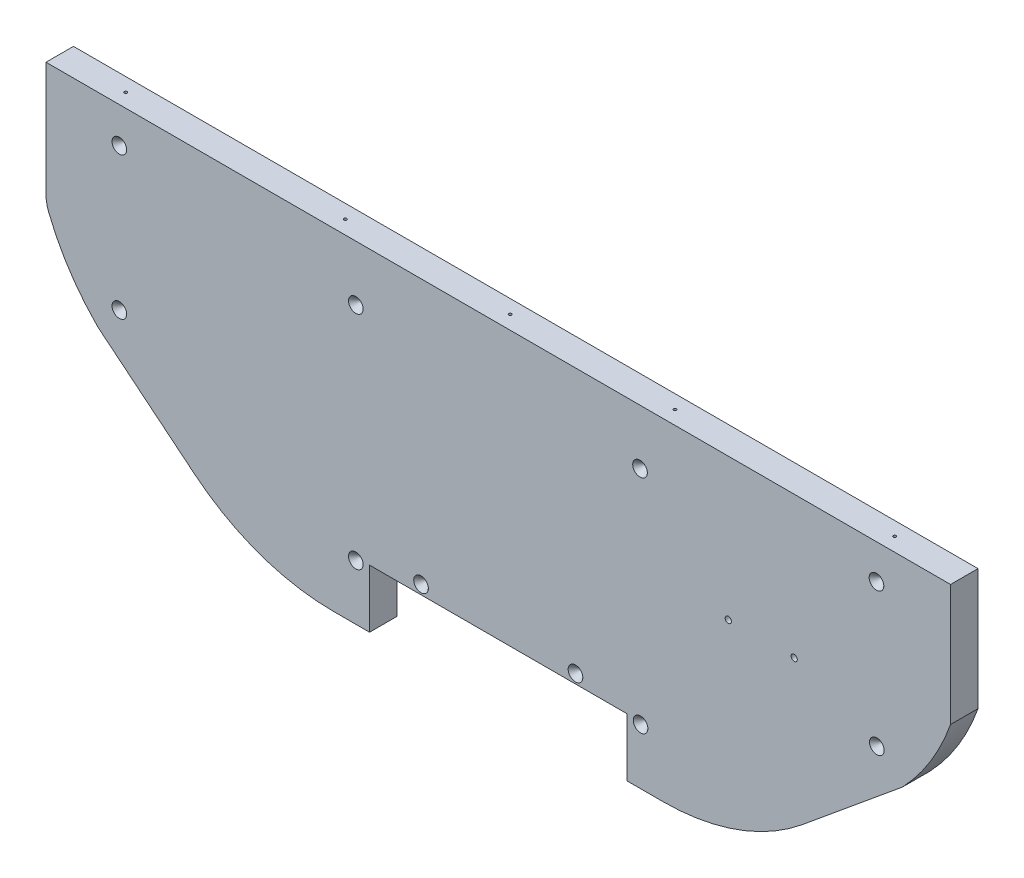
SolidWorks part; units mm, degrees
material "MDF"
ref_plane "Front Plane" through (0, 0, 0) normal (0, 0, 1) x (1, 0, 0)
ref_plane "Top Plane" through (0, 0, 0) normal (0, 1, 0) x (1, 0, 0)
ref_plane "Right Plane" through (0, 0, 0) normal (1, 0, 0) x (0, 0, -1)
sketch "Sketch1" plane through (0, 0, 0) normal (0, 0, 1) x (1, 0, 0)
  line L0 (-394.3667, -87.3125) -> (-394.3667, 23.8125) construction
  line L2 (-618.7885, -233.3625) -> (-593.7568, -233.3625) construction
  line L3 (-394.3667, -87.3125) -> (-394.3667, -3.175)
  line L4 (-497.3744, -199.0142) -> (-427.755, -141.5981)
  line L5 (-709.3267, -233.3625) -> (-593.7568, -233.3625)
  line L6 (-709.3267, -3.175) -> (-709.3267, -233.3625) construction
  line L7 (-1021.7467, -3.175) -> (-396.9067, -3.175) construction
  line L8 (-394.3667, -3.175) -> (-709.3267, -3.175)
  line L9 (-1021.7467, -3.175) -> (-396.9067, -3.175) construction
  line L10 (-976.0267, -152.2395) -> (-918.7391, -199.0142) construction
  line L11 (-1021.7467, -87.3125) -> (-1021.7467, -20.955) construction
  line L12 (-985.5517, -144.4625) -> (-918.7391, -199.0142)
  line L13 (-1021.7467, -87.3125) -> (-1021.7467, -3.175)
  line L14 (-822.3567, -233.3625) -> (-709.3267, -233.3625)
  line L15 (-709.3267, -3.175) -> (-1021.7467, -3.175)
  arc A0 (-427.755, -141.5981) -> (-394.3667, -87.3125) centre (-538.0037, -36.3792) ccw construction
  arc A1 (-593.7568, -233.3625) -> (-497.3744, -199.0142) centre (-593.7568, -80.9625) ccw construction
  arc A2 (-427.755, -141.5981) -> (-394.3667, -87.3125) centre (-538.0037, -36.3792) ccw
  arc A3 (-593.7568, -233.3625) -> (-497.3744, -199.0142) centre (-593.7568, -80.9625) ccw
  arc A4 (-918.7391, -199.0142) -> (-822.3567, -233.3625) centre (-822.3567, -80.9625) ccw construction
  arc A5 (-1021.7467, -87.3125) -> (-985.5517, -144.4625) centre (-878.1098, -36.3792) ccw construction
  arc A6 (-918.7391, -199.0142) -> (-822.3567, -233.3625) centre (-822.3567, -80.9625) ccw
  arc A7 (-1021.7467, -87.3125) -> (-985.5517, -144.4625) centre (-878.1098, -36.3792) ccw
  point P13 (-709.3267, -3.175)
extrude "Boss-Extrude1" add sketch "Sketch1" along normal blind 19.05
hole_wizard "5/64 (0.07813) Diameter Hole1" positions "Sketch2" profile "Sketch3" hole size "5/64" standard "ANSI Inch"
sketch "Sketch2" plane through (-708.0567, 15.875, 6128.5599) normal (0, 1, 0) x (1, 0, 0)
  line L1 (-1.27, 6109.5099) -> (-1.27, 6338.7449) construction
  point P0 (-262.8265, 6157.4524)
  point P6 (-98.7933, 6157.4524)
  point P18 (-262.8265, 6233.6524)
  point P19 (-98.7933, 6233.6524)
  point P22 (-262.8265, 6309.8524)
  point P23 (-98.7933, 6309.8524)
  point P24 (-267.97, 6119.0349)
  point P34 (-115.57, 6119.0349)
  point P37 (-1.27, 6119.0349)
  point P40 (113.03, 6119.0349)
  point P44 (265.43, 6119.0349)
  point P55 (96.2533, 6309.8524)
  point P56 (260.2865, 6309.8524)
  point P59 (96.2533, 6233.6524)
  point P60 (260.2865, 6233.6524)
  point P63 (96.2533, 6157.4524)
  point P64 (260.2865, 6157.4524)
sketch "Sketch3" plane through (-970.8832, 15.875, -28.8925) normal (1, 0, 0) x (0, 0, 1)
  line L0 (0, 0) -> (0, 38.6962)
  line L1 (0, 38.6962) -> (0.9923, 38.1)
  line L2 (0.9923, 38.1) -> (0.9923, 4.7024)
  line L3 (0.9923, 4.7024) -> (5.08, 0)
  line L4 (5.08, 0) -> (0, 0)
  line L5 (-0.9923, 4.7024) -> (-5.08, 0) construction
  line L6 (0, 38.6962) -> (-0.9923, 38.1) construction
  line L7 (0, -6.35) -> (0, 107.95) construction
  dimension "Hole Dia." = 1.9845
  dimension "Hole Depth" = 38.1
  dimension "Near C'Sink Dia." = 10.16
  dimension "Near C'Sink Angle" = 82
  dimension "Drill Angle" = 118
hole_wizard "5/64 (0.07813) Diameter Hole2" positions "Sketch4" profile "Sketch5" hole size "5/64" standard "ANSI Inch"
sketch "Sketch4" plane through (-708.0567, 1936.854, 19.05) normal (0, 0, 1) x (-1, 0, 0)
  line L23 (262.8265, 2088.1084) -> (262.8265, 2038.7486)
  line L24 (262.8265, 2038.7486) -> (262.8265, 1989.3888)
  line L25 (262.8265, 1989.3888) -> (262.8265, 2038.7486)
  line L26 (262.8265, 2038.7486) -> (262.8265, 1989.3888)
  line L27 (262.8265, 1989.3888) -> (262.8265, 1940.029)
  line L33 (98.7933, 2170.2165) -> (98.7933, 2131.8519)
  line L35 (98.7933, 2131.8519) -> (98.7933, 2093.4873)
  line L36 (98.7933, 2093.4873) -> (98.7933, 2055.1227)
  line L37 (98.7933, 2055.1227) -> (98.7933, 2016.7581)
  line L38 (98.7933, 2016.7581) -> (98.7933, 1978.3935)
  line L39 (98.7933, 1978.3935) -> (98.7933, 1940.029)
  line L44 (89.2683, 2123.544) -> (53.561, 2123.544)
  line L46 (53.561, 2123.544) -> (17.8537, 2123.544)
  line L47 (17.8537, 2123.544) -> (-17.8537, 2123.544)
  line L48 (-17.8537, 2123.544) -> (-53.561, 2123.544)
  line L49 (-53.561, 2123.544) -> (-89.2683, 2123.544)
  line L53 (0, 2170.2165) -> (0.2777, 1940.029) construction
  line L55 (-98.3301, 1978.1557) -> (-98.2375, 1939.7912)
  line L56 (-98.4227, 2016.5202) -> (-98.3301, 1978.1557)
  line L57 (-98.5153, 2054.8846) -> (-98.4227, 2016.5202)
  line L58 (-98.6078, 2093.2491) -> (-98.5153, 2054.8846)
  line L59 (-98.7004, 2131.6136) -> (-98.6078, 2093.2491)
  line L60 (-98.793, 2169.978) -> (-98.7004, 2131.6136)
  line L61 (-262.3894, 1988.755) -> (-262.2702, 1939.3954)
  line L62 (-262.5085, 2038.1147) -> (-262.3894, 1988.755)
  line L63 (-262.3894, 1988.755) -> (-262.5085, 2038.1147)
  line L64 (-262.5085, 2038.1147) -> (-262.3894, 1988.755)
  line L65 (-262.6276, 2087.4744) -> (-262.5085, 2038.1147)
  point P71 (262.8265, 1964.7089)
  point P79 (262.8265, 2063.4285)
  point P95 (98.7933, 2131.8519)
  point P103 (98.7933, 1978.3935)
  point P126 (53.561, 2123.544)
  point P134 (-53.561, 2123.544)
  point P162 (-98.3301, 1978.1557)
  point P166 (-98.7004, 2131.6136)
  point P167 (-262.568, 2062.7945)
  point P169 (-262.3298, 1964.0752)
sketch "Sketch5" plane through (-445.727, -27.2212, 19.05) normal (1, 0, 0) x (0, -1, 0)
  line L0 (0, 0) -> (0, 38.6962)
  line L1 (0, 38.6962) -> (0.9923, 38.1)
  line L2 (0.9923, 38.1) -> (0.9923, 4.7024)
  line L3 (0.9923, 4.7024) -> (5.08, 0)
  line L4 (5.08, 0) -> (0, 0)
  line L5 (-0.9923, 4.7024) -> (-5.08, 0) construction
  line L6 (0, 38.6962) -> (-0.9923, 38.1) construction
  line L7 (0, -6.35) -> (0, 107.95) construction
  dimension "Hole Dia." = 1.9845
  dimension "Hole Depth" = 38.1
  dimension "Near C'Sink Dia." = 10.16
  dimension "Near C'Sink Angle" = 82
  dimension "Drill Angle" = 118
sketch "Sketch6" plane through (0, 0, 0) normal (0, 0, -1) x (-1, 0, 0)
  line L1 (797.325, -233.3625) -> (618.7884, -233.3625)
  line L2 (797.325, -233.3625) -> (797.325, -193.04)
  line L3 (797.325, -193.04) -> (618.7884, -193.04)
  line L4 (618.7884, -233.3625) -> (618.7884, -193.04)
extrude "Cut-Extrude1" cut sketch "Sketch6" against normal up to next
fillet "Fillet1" radius 25.4 2 edges at (-985.5517, -144.4625, 9.525) (-1021.7467, -87.3125, 9.525)
hole_wizard "#6 Clearance Hole1" positions "Sketch7" profile "Sketch8" hole size "#6" standard "ANSI Inch" end condition up to next
sketch "Sketch7" plane through (0, 0, 19.05) normal (0, 0, 1) x (1, 0, 0)
  arc A0 (-504.7297, -98.0667) -> (-504.7297, -104.8742) centre (-502.7993, -101.4705) ccw construction
  arc A1 (-550.4497, -98.0667) -> (-550.4497, -104.8742) centre (-548.5193, -101.4705) ccw construction
  point P0 (-502.7993, -101.4705)
  point P2 (-548.5193, -101.4705)
  point P5 (0, 0)
  point P9 (0, 0)
sketch "Sketch8" plane through (-502.7993, -101.4705, 19.05) normal (1, 0, 0) x (0, -1, 0)
  line L0 (0, 0) -> (0, 19.05)
  line L1 (0, 19.05) -> (2.1526, 19.05)
  line L2 (2.1526, 19.05) -> (2.1526, 0)
  line L5 (2.1526, 0) -> (0, 0)
  line L11 (0, -6.35) -> (0, 107.95) construction
  dimension "Thru Hole Dia." = 4.3053
  dimension "Thru Hole Depth" = 19.05
